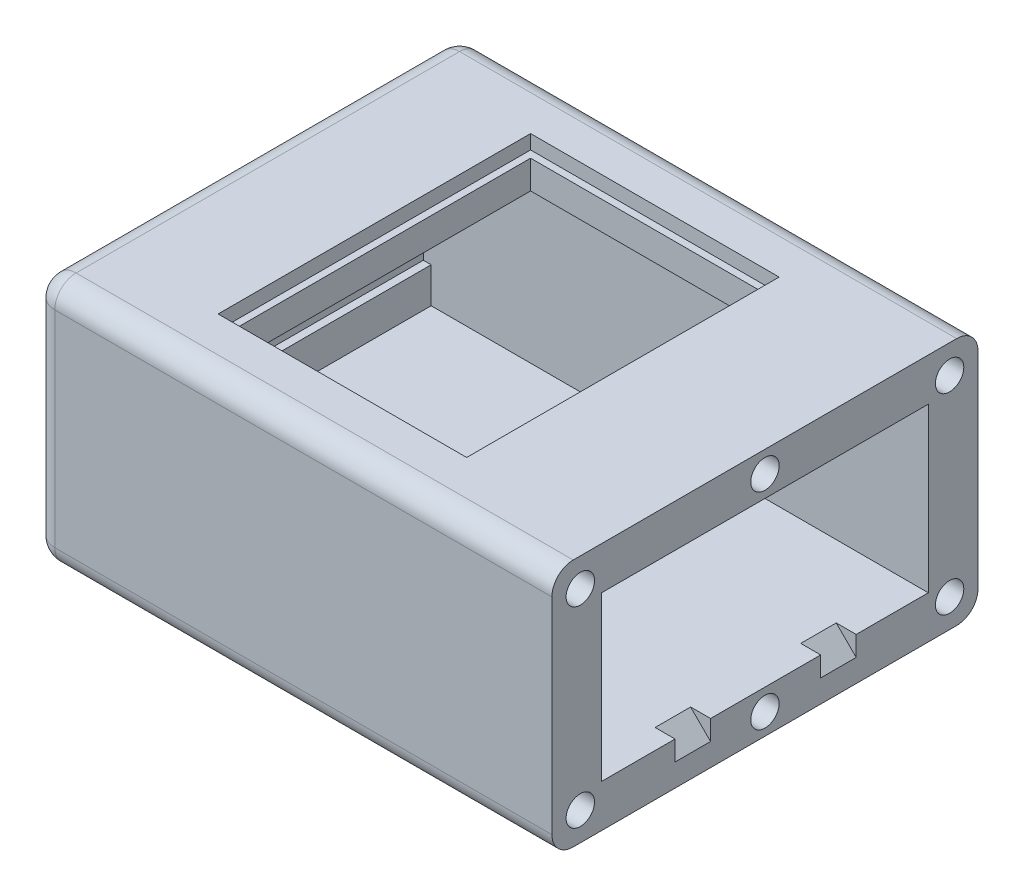
SolidWorks part; units mm, degrees
note: The reader was unsure of these and kept them because the rebuilt part matched: shared geometry of "Sketch1<3>", "Sketch5<3>".
ref_plane "Front Plane" through (0, 0, 0) normal (0, 0, 1) x (1, 0, 0)
ref_plane "Top Plane" through (0, 0, 0) normal (0, 1, 0) x (1, 0, 0)
ref_plane "Right Plane" through (0, 0, 0) normal (1, 0, 0) x (0, 0, -1)
sketch "Sketch1" plane through (0, 0, 0) normal (1, 0, 0) x (0, 0, -1)
  line L0 (-1000, 0) -> (49000, 0) construction
  line L1 (-30, -17.5) -> (30, -17.5)
  line L2 (-30, -17.5) -> (-30, 17.5)
  line L3 (-30, 17.5) -> (30, 17.5)
  line L4 (30, -17.5) -> (30, 17.5)
  line L5 (0, -1000) -> (0, 49000) construction
  line L7 (-23, 11.5) -> (23, 11.5)
  line L8 (-23, 11.5) -> (-23, -11.5)
  line L9 (-23, -11.5) -> (23, -11.5)
  line L10 (23, 11.5) -> (23, -11.5)
  circle A0 centre (-26, 13.5) radius 2
  circle A1 centre (0, 14.5) radius 2
  circle A2 centre (26, 13.5) radius 2
  circle A3 centre (0, -14.5) radius 2
  circle A4 centre (26, -13.5) radius 2
  circle A5 centre (-26, -13.5) radius 2
  dimension "D1" = 4
  dimension "D2" = 4
  dimension "D5" = 4
  dimension "D6" = 4
  dimension "D7" = 4
  dimension "D8" = 3
  dimension "D9" = 4
  dimension "D10" = 4
  dimension "D11" = 4
  dimension "D12" = 4
  dimension "D13" = 3
  dimension "D14" = 3
  dimension "D15" = 3
  dimension "D16" = 3
  dimension "D17" = 3
  dimension "D3" = 46
  dimension "D4" = 23
extrude "Boss-Extrude1" add sketch "Sketch1" against normal blind 73 contours A1 | L1 L4 L3 L2 A5 A4 A3 A2 A1 A0 L7 L10 L9 L8 | A0 | A5 | A3 | A4 | L10 L7 L8 L9 | A2
sketch "Sketch2" plane through (-73, 0, 0) normal (-1, 0, 0) x (0, 0, 1)
  line L1 (-23, 11.5) -> (23, 11.5)
  line L2 (-23, 11.5) -> (-23, -11.5)
  line L3 (-23, -11.5) -> (23, -11.5)
  line L4 (23, 11.5) -> (23, -11.5)
extrude "Boss-Extrude2" add sketch "Sketch2" against normal blind 3
extrude "Cut-Extrude1" cut sketch "Sketch1<3>" against normal blind 4.8 contours A0 | A1 | A2 | A3 | A5 | A4
sketch "Sketch1<3>" plane through (0, 0, 0) normal (1, 0, 0) x (0, 0, -1) same geometry as "Sketch1"
fillet "Fillet1" radius 3 8 edges at (-73, 0, -30) (-73, 17.5, 0) (-73, 0, 30) (-73, -17.5, 0) (-36.5, 17.5, -30) (-36.5, -17.5, -30) (-36.5, -17.5, 30) (-36.5, 17.5, 30)
sketch "Sketch3" plane through (-70, 0, 0) normal (1, 0, 0) x (0, 0, -1)
  line L0 (-23, 11.5) -> (-23, -11.5) construction
  line L1 (-23, -4) -> (23, -4)
  line L2 (-23, -4) -> (-23, -6.5)
  line L3 (-23, -6.5) -> (23, -6.5)
  line L4 (23, -4) -> (23, -6.5)
  line L5 (23, 11.5) -> (23, -11.5) construction
  line L6 (-23, 11.5) -> (23, 11.5) construction
  dimension "D1" = 18
  dimension "D2" = 2.5
extrude "Cut-Extrude2" cut sketch "Sketch3" against normal blind 1.1
sketch "Sketch5" plane through (0, 17.5, 0) normal (0, 1, 0) x (1, 0, 0)
  line L0 (0, 27) -> (-70, 27) construction
  line L1 (-55, 22) -> (-20, 22)
  line L2 (-55, 22) -> (-55, -22)
  line L3 (-55, -22) -> (-20, -22)
  line L4 (-20, 22) -> (-20, -22)
  line L5 (-70, -27) -> (0, -27) construction
  line L6 (-70, 27) -> (-70, -27) construction
  line L7 (0, -27) -> (0, 27) construction
  line L8 (-54, 21) -> (-21, 21)
  line L9 (-21, 21) -> (-21, -21)
  line L10 (-54, -21) -> (-21, -21)
  line L11 (-54, 21) -> (-54, -21)
  dimension "D1" = 5
  dimension "D2" = 5
  dimension "D3" = 15
  dimension "D4" = 20
  dimension "D5" = 1
extrude "Cut-Extrude5" cut sketch "Sketch5" against normal blind 10 contours L8 L11 L10 L9
extrude "Cut-Extrude6" cut sketch "Sketch5<3>" against normal blind 2 contours L4 L1 L2 L3 L11 L8 L9 L10
sketch "Sketch5<3>" plane through (0, 17.5, 0) normal (0, 1, 0) x (1, 0, 0) same geometry as "Sketch5"
sketch "Sketch7" plane through (0, 0, 12.159) normal (0, 0, 1) x (1, 0, 0)
  line L0 (0, -11) -> (0, -14.3071)
  line L1 (0, -13.6) -> (0, -6.6) construction
  line L2 (0, -14.3071) -> (-3.3071, -11)
  line L4 (-3.3071, -11) -> (0, -11)
  line L5 (-5, -8.6) -> (0, -13.6) construction
  point P6 (0, 0)
  point P8 (0, 0)
  point P10 (0, -11.4858)
  point P11 (0, -11.5)
  point P12 (0, -11.31)
  dimension "D1" = 0.5
  dimension "D2" = 0.5
extrude "Cut-Extrude8" cut sketch "Sketch7" against normal blind 4.5 and the other way blind 0.5 contours L4 L0 L2
sketch "Sketch8" plane through (0, 0, -12.3454) normal (0, 0, -1) x (-1, 0, 0)
  line L0 (0, -11) -> (3.3071, -11)
  line L1 (3.3071, -11) -> (0, -14.3071)
  line L2 (0, -14.3071) -> (0, -11)
extrude "Cut-Extrude9" cut sketch "Sketch8" against normal blind 4.5 and the other way blind 0.5
equation "\"D12@Sketch1\"=\"D5@Sketch1\""
equation "\"D11@Sketch1\"=\"D5@Sketch1\""
equation "\"D9@Sketch1\"=\"D5@Sketch1\""
equation "\"D10@Sketch1\"=\"D5@Sketch1\""
equation "\"D6@Sketch1\"=\"D5@Sketch1\""
equation "\"D7@Sketch1\"=\"D5@Sketch1\""
